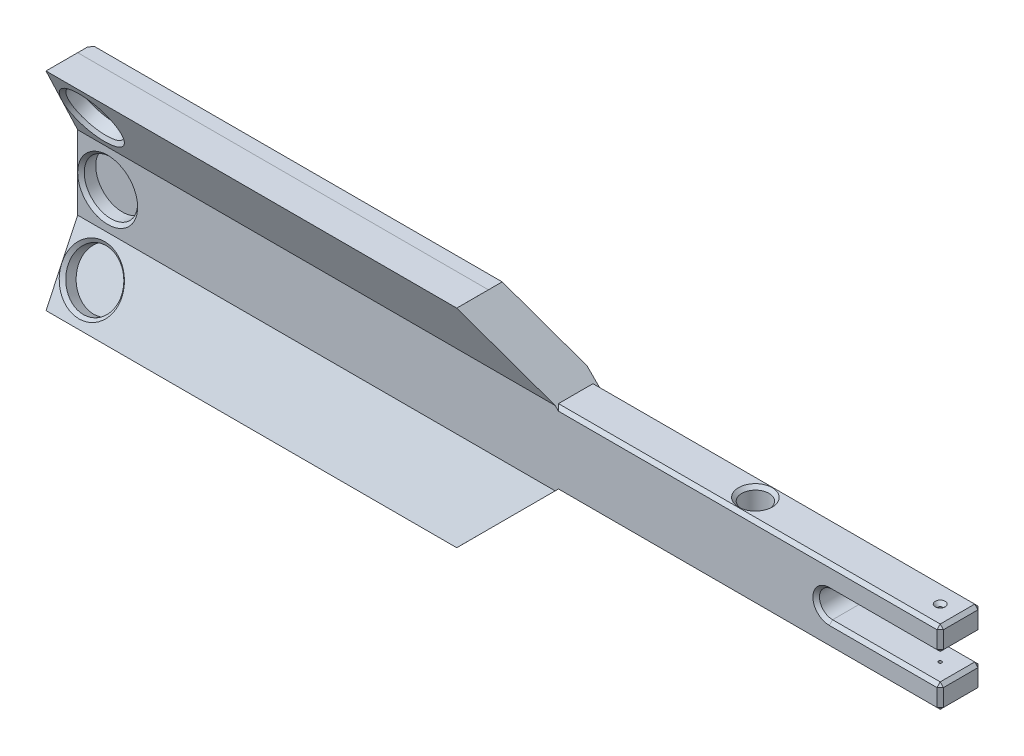
SolidWorks part; units mm, degrees
ref_plane "Front" through (0, 0, 0) normal (0, 0, 1) x (1, 0, 0)
ref_plane "Top" through (0, 0, 0) normal (0, 1, 0) x (1, 0, 0)
ref_plane "Right" through (0, 0, 0) normal (1, 0, 0) x (0, 0, -1)
sketch "Sketch1" plane through (0, 0, 0) normal (0, 0, 1) x (1, 0, 0)
  line L1 (52.5, -4.5) -> (-52.5, -4.5)
  line L2 (52.5, -4.5) -> (52.5, 4.5)
  line L3 (52.5, 4.5) -> (-52.5, 4.5)
  line L4 (-52.5, -4.5) -> (-52.5, 4.5)
  line L5 (52.5, -4.5) -> (-52.5, 4.5) construction
  line L6 (52.5, 4.5) -> (-52.5, -4.5) construction
  point P0 (0, 0)
  dimension "D1" = 9
  dimension "D2" = 105
extrude "Boss-Extrude1" add sketch "Sketch1" along normal blind 5
sketch "Sketch2" plane through (0, 4.5, 0) normal (0, 1, 0) x (1, 0, 0)
  line L0 (52.5, -5) -> (52.5, 0) construction
  line L2 (52.5, 0) -> (-52.5, 0) construction
  circle A0 centre (27.5, -2.5) radius 1.65
  dimension "D3" = 3.3
  dimension "D1" = 2.5
  dimension "D2" = 25
sketch "Sketch4" plane through (0, 0, 5) normal (0, 0, 1) x (1, 0, 0)
  line L0 (39, 0) -> (45, 0) construction
  line L1 (39, 1.6) -> (45, 1.6)
  line L2 (39, -1.6) -> (45, -1.6)
  arc A0 (39, 1.6) -> (39, -1.6) centre (39, 0) ccw
  arc A1 (45, -1.6) -> (45, 1.6) centre (45, 0) ccw
  point P2 (42, 0)
  dimension "D1" = 1.6
  dimension "D2" = 42
  dimension "D3" = 6
extrude "Cut-Extrude1" cut sketch "Sketch4" against normal blind 5
sketch "Sketch14" plane through (0, 0, 5) normal (0, 0, 1) x (1, 0, 0)
  line L0 (39, -1.6) -> (45, -1.6) construction
  line L1 (44.5, -1.6) -> (52.5, -1.6)
  line L2 (44.5, -1.6) -> (44.5, 1.6)
  line L3 (44.5, 1.6) -> (52.5, 1.6)
  line L4 (52.5, -1.6) -> (52.5, 1.6)
  line L5 (52.5, -4.5) -> (52.5, 4.5) construction
  line L6 (45, 1.6) -> (39, 1.6) construction
  dimension "D1" = 8
extrude "Cut-Extrude7" cut sketch "Sketch14" against normal blind 10
sketch "Sketch8" plane through (0, 0, 0) normal (0, 0, -1) x (-1, 0, 0)
  line L0 (52.5, 4.5) -> (52.5, -4.5) construction
  line L1 (52.5, 12.63) -> (2.5, 12.63)
  line L2 (52.5, 12.63) -> (52.5, -12.63)
  line L3 (52.5, -12.63) -> (2.5, -12.63)
  line L4 (2.5, 12.63) -> (2.5, -12.63)
  line L6 (-52.5, 4.5) -> (52.5, 4.5) construction
  dimension "D1" = 25.26
  dimension "D2" = 8.13
  dimension "D3" = 50
extrude "Boss-Extrude3" add sketch "Sketch8" against normal up to surface (5 mm away) up to face at (22.675, 0, 5)
sketch "Sketch9" plane through (-52.5, 0, 0) normal (-1, 0, 0) x (0, 0, 1)
  line L0 (5, 12.63) -> (5, -12.63) construction
  line L1 (5, 12.6327) -> (8.8548, 12.6327)
  line L2 (8.8548, 12.6327) -> (5, 4.5)
  line L3 (5, 4.5) -> (5, 12.6327)
  line L4 (-3.9634, 0) -> (12.9509, 0) construction
  line L5 (8.8548, -12.6327) -> (5, -4.5)
  line L6 (5, -12.6327) -> (8.8548, -12.6327)
  line L7 (5, -4.5) -> (5, -12.6327)
  circle A0 centre (25, 0) radius 20 construction
  dimension "D1" = 40
  dimension "D2" = 9
  dimension "D3" = 9
extrude "Boss-Extrude4" add sketch "Sketch9" against normal up to surface (50 mm away) up to face at (-2.5, 8.565, 2.5)
sketch "Sketch13" plane through (-52.5, 0, 0) normal (-1, 0, 0) x (0, 0, 1)
  line L0 (0, 5.625) -> (3.3203, 12.63)
  line L1 (0, 12.63) -> (0, -12.63) construction
  line L2 (5, 12.63) -> (0, 12.63) construction
  line L3 (3.3203, 12.63) -> (-2, 12.63)
  line L4 (-2, 12.63) -> (-2, -12.63)
  line L5 (-2, -12.63) -> (3.3203, -12.63)
  line L6 (5, -12.63) -> (0, -12.63) construction
  line L7 (3.3203, -12.63) -> (0, -5.625)
  line L8 (0, -5.625) -> (0, 5.625)
  line L10 (5, 4.5) -> (8.8548, 12.6327) construction
  line L11 (8.8548, -12.6327) -> (5, -4.5) construction
  dimension "D1" = 5
  dimension "D2" = 5
  dimension "D3" = 2
extrude "Cut-Extrude6" cut sketch "Sketch13" against normal through all
chamfer "Chamfer4" distance 8.13 2 edges at (-2.5, 4.5, 2.5) (-2.5, -4.5, 2.5)
sketch "Sketch10" plane through (-52.5, 0, 0) normal (-1, 0, 0) x (0, 0, 1)
  line L0 (5, 4.5) -> (5, -4.5) construction
  line L1 (5, 4.5) -> (8.8548, 12.6327) construction
  line L2 (8.8548, -12.6327) -> (5, -4.5) construction
  circle A0 centre (25, 0) radius 20
sketch "Sketch11" plane through (0, 0, 5) normal (0, 0, 1) x (1, 0, 0)
  line L2 (-52.5, 4.5) -> (-52.5, -4.5) construction
  circle A0 centre (-48.85, 0) radius 3.25
  dimension "D1" = 6.5
  dimension "D2" = 3.65
extrude "Cut-Extrude3" cut sketch "Sketch11" against normal blind 1.8
sketch "Sketch12" plane through (0, -1.1096, 2.341) normal (0, -0.4283, 0.9036) x (1, 0, 0)
  line L1 (-2.5, 15.2079) -> (-52.5, 15.2079) construction
  line L2 (-52.5, 30.7079) -> (-52.5, -9.2921) construction
  circle A0 centre (-48.85, 10.7079) radius 3.25
  dimension "D1" = 6.5
  dimension "D2" = 4.5
  dimension "D3" = 3.65
extrude "Cut-Extrude4" cut sketch "Sketch12" against normal blind 1.8
mirror "Mirror2" about plane through (0, 0, 0) normal (0, 1, 0) of "Cut-Extrude4"
chamfer "Chamfer2" distance 0.4 angle 45 3 edges at (-45.6, 0, 5) (-48.85, -5.6295, 5.5354) (-48.85, 5.6295, 5.5354)
ref_plane "Plane1" through (-48.5, 0, 0) normal (-1, 0, 0) x (0, 0, 1)
extrude "Cut-Extrude5" cut sketch "Sketch2" against normal blind 10
chamfer "Chamfer5" distance 0.4 angle 45 20 edges at (25.85, -4.5, 2.5) (25.85, 4.5, 2.5) (52.5, 4.5, 2.5) (29.065, 4.5, 5) (52.5, 3.05, 5) (52.5, -3.05, 5) (29.065, -4.5, 5) (52.5, -4.5, 2.5) (29.065, 4.5, 0) (29.065, -4.5, 0) (52.5, 3.05, 0) (52.5, -3.05, 0) (45.75, -1.6, 0) (37.4, 0, 0) (45.75, 1.6, 0) (45.75, 1.6, 5) (37.4, 0, 5) (45.75, -1.6, 5) (52.5, 1.6, 2.5) (52.5, -1.6, 2.5)
chamfer "Chamfer6" distance 0.4 angle 45 3 edges at (-52.5, 9.1275, 1.6602) (-52.5, -9.1275, 1.6602) (-52.5, 0, 0)
sketch "Sketch15" plane through (0, -4.5, 0) normal (0, -1, 0) x (1, 0, 0)
  line L0 (52.5, 4.6) -> (52.5, 0.4) construction
  line L1 (52.1, 0) -> (6.03, 0) construction
  circle A0 centre (50, 2.5) radius 0.2
  dimension "D1" = 0.4
  dimension "D2" = 2.5
  dimension "D3" = 2.5
extrude "Cut-Extrude8" cut sketch "Sketch15" against normal blind 10
chamfer "Chamfer7" distance 0.4 angle 45 2 edges at (50.2, 4.5, 2.5) (50.2, -4.5, 2.5)
